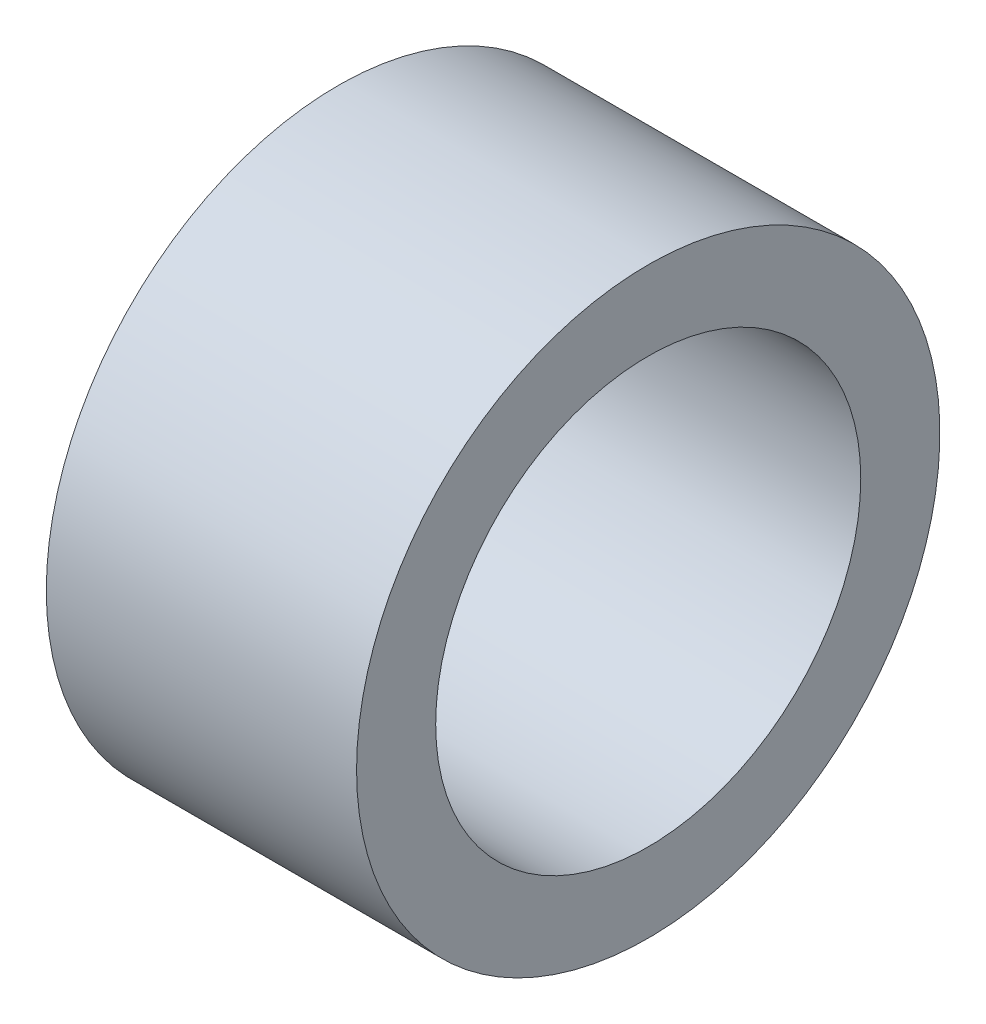
SolidWorks part; units mm, degrees
material "Nylon 6/10"
ref_plane "Front Plane" through (0, 0, 0) normal (0, 0, 1) x (1, 0, 0)
ref_plane "Top Plane" through (0, 0, 0) normal (0, 1, 0) x (1, 0, 0)
ref_plane "Right Plane" through (0, 0, 0) normal (1, 0, 0) x (0, 0, -1)
sketch "Sketch1" plane through (0, 0, 0) normal (0, 0, 1) x (1, 0, 0)
  line L0 (31.75, -11.7723) -> (31.75, 10.1777) construction
  line L1 (31.75, 5.969) -> (38.1, 5.969)
  line L2 (31.75, 5.969) -> (31.75, 4.3498)
  line L3 (31.75, 4.3498) -> (38.1, 4.3498)
  line L4 (38.1, 5.969) -> (38.1, 4.3498)
  line L5 (0, 0) -> (42.6651, 0) construction
  line L7 (50.5354, 3.9688) -> (-48.4378, 3.9688) construction
  dimension "D1" = 0.381
  dimension "D2" = 11.938
  dimension "D3" = 6.35
revolve "Revolve1" add sketch "Sketch1" angle 360 about L5
